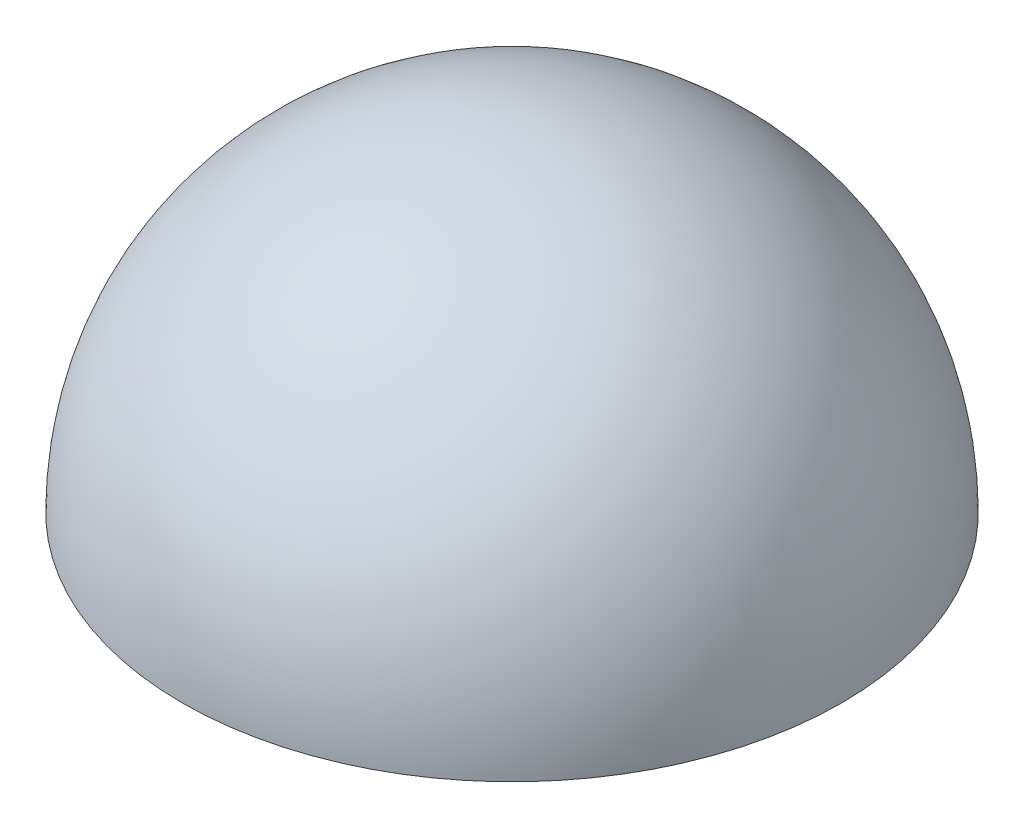
SolidWorks part; units mm, degrees
ref_plane "前视基准面" through (0, 0, 0) normal (0, 0, 1) x (1, 0, 0)
ref_plane "上视基准面" through (0, 0, 0) normal (0, 1, 0) x (1, 0, 0)
ref_plane "右视基准面" through (0, 0, 0) normal (1, 0, 0) x (0, 0, -1)
sketch "草图1" plane through (0, 0, 0) normal (0, 0, 1) x (1, 0, 0)
  line L0 (-25, 0) -> (25, 0)
  line L1 (0, 0) -> (0, 25)
  arc A0 (25, 0) -> (-25, 0) centre (0, 0) ccw
revolve "旋转1" add sketch "草图1" angle 360 about L1 region at (-10.6103, 10.6103, 0)
